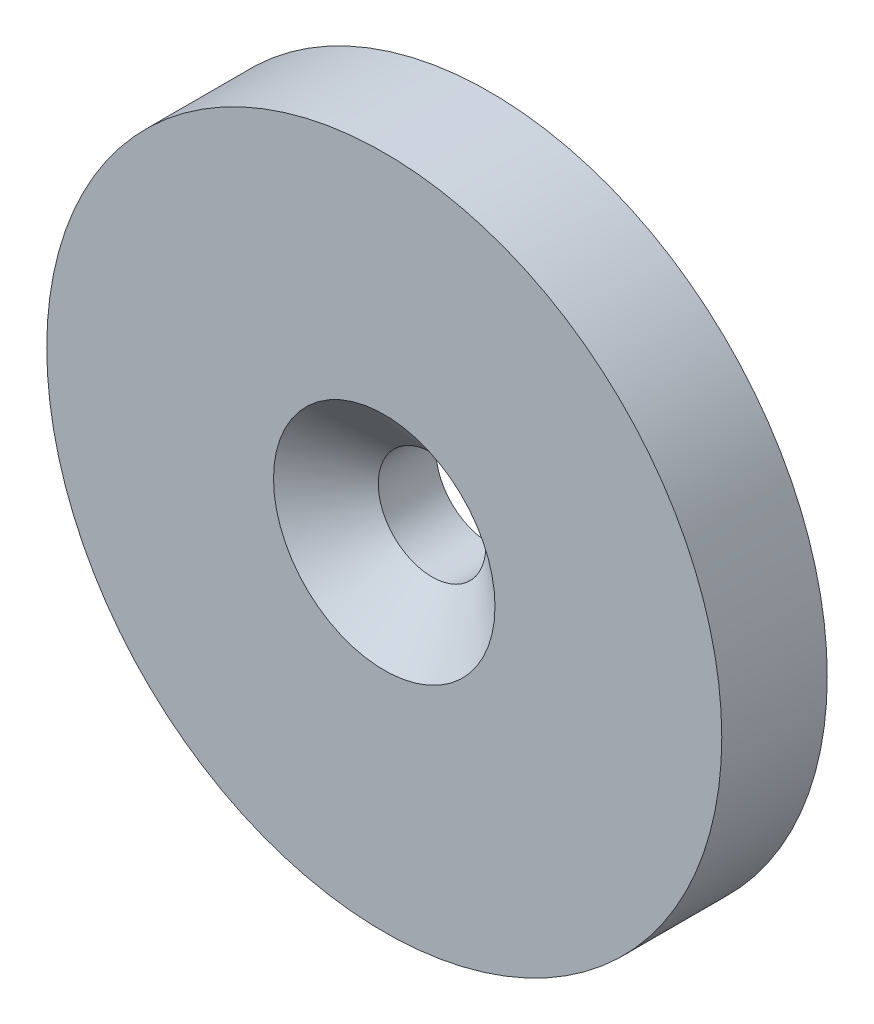
SolidWorks part; units mm, degrees
ref_plane "Plan de face" through (0, 0, 0) normal (0, 0, 1) x (1, 0, 0)
ref_plane "Plan de dessus" through (0, 0, 0) normal (0, 1, 0) x (1, 0, 0)
ref_plane "Plan de droite" through (0, 0, 0) normal (1, 0, 0) x (0, 0, -1)
sketch "Sketch1" plane through (0, 0, 0) normal (0, 0, 1) x (1, 0, 0)
  circle A0 centre (-29.5037, 20.7668) radius 16
  dimension "D1" = 32
extrude "Boss-Extrude1" add sketch "Sketch1" along normal blind 5
sketch "Sketch3" plane through (0, 0, 5) normal (0, 0, 1) x (1, 0, 0)
  circle A0 centre (-29.5037, 20.7668) radius 5.25
  circle A3 centre (-29.5037, 20.7668) radius 16 construction
  dimension "D1" = 10.5
  dimension "D2" = 0
hole_wizard "CSK for #1 Flat Head Machine Screw (100)1" positions "3DSketch1" profile "Sketch5" countersink size "#1" standard "ANSI Inch" end condition through all
sketch3d "3DSketch1"
  point P0 (-29.5037, 20.7668, 5)
sketch "Sketch5" plane through (-29.5037, 20.7668, 5) normal (1, 0, 0) x (0, -1, 0)
  line L0 (0, 0) -> (0, 5)
  line L1 (0, 5) -> (2.55, 5)
  line L2 (2.55, 5) -> (2.55, 2.2656)
  line L3 (2.55, 2.2656) -> (5.25, 0)
  line L5 (5.25, 0) -> (0, 0)
  line L6 (-2.55, 2.2656) -> (-5.25, 0) construction
  line L11 (0, -6.35) -> (0, 107.95) construction
  dimension "Thru Hole Dia." = 5.1
  dimension "Thru Hole Depth" = 5
  dimension "Near C'Sink Dia." = 10.5
  dimension "Near C'Sink Angle" = 100
